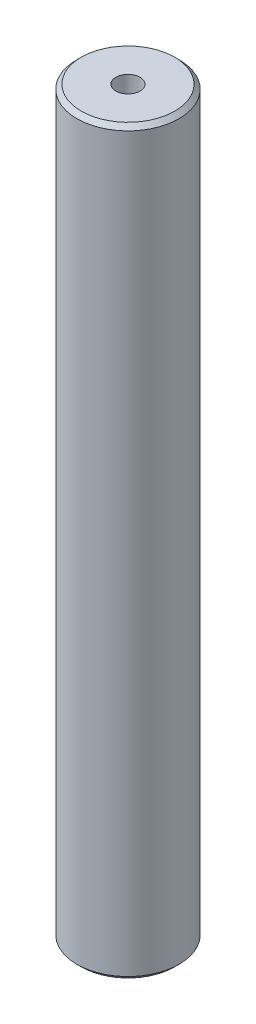
SolidWorks part; units mm, degrees
ref_plane "Front Plane" through (0, 0, 0) normal (0, 0, 1) x (1, 0, 0)
ref_plane "Top Plane" through (0, 0, 0) normal (0, 1, 0) x (1, 0, 0)
ref_plane "Right Plane" through (0, 0, 0) normal (1, 0, 0) x (0, 0, -1)
sketch "Sketch1" plane through (0, 0, 0) normal (0, 1, 0) x (1, 0, 0)
  circle A0 centre (0, 0) radius 5
  dimension "SHAFT_OD" = 10
extrude "Boss-Extrude1" add sketch "Sketch1" along normal blind 72.5307
sketch "Sketch2" plane through (0, 0, 0) normal (0, 1, 0) x (1, 0, 0)
  circle A0 centre (0, 0) radius 1.1801
  dimension "BORE_D" = 2.3603
extrude "Cut-Extrude1" cut sketch "Sketch2" along normal through all
chamfer "Chamfer1" distance 0.4261 angle 45 2 edges at (0, 72.5307, 5) (0, 0, 5)
